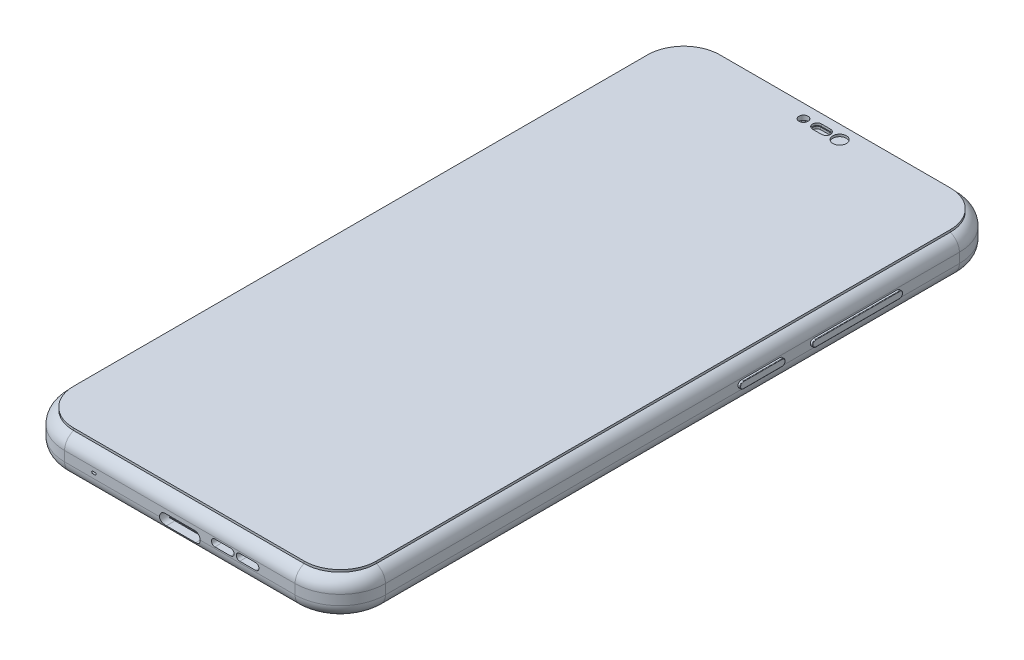
SolidWorks part; units mm, degrees
other "Camera1"
material "PMMA"
ref_plane "Front Plane" through (0, 0, 0) normal (0, 0, 1) x (1, 0, 0)
ref_plane "Top Plane" through (0, 0, 0) normal (0, 1, 0) x (1, 0, 0)
ref_plane "Right Plane" through (0, 0, 0) normal (1, 0, 0) x (0, 0, -1)
sketch "Sketch1" plane through (0, 0, 0) normal (0, 1, 0) x (1, 0, 0)
  line L1 (-25.5, 73.5) -> (25.5, 73.5)
  line L2 (-35.5, 63.5) -> (-35.5, -63.5)
  line L3 (-25.5, -73.5) -> (25.5, -73.5)
  line L4 (35.5, 63.5) -> (35.5, -63.5)
  line L5 (-35.5, 73.5) -> (35.5, -73.5) construction
  line L6 (-35.5, -73.5) -> (35.5, 73.5) construction
  arc A0 (-35.5, -63.5) -> (-25.5, -73.5) centre (-25.5, -63.5) ccw
  arc A1 (25.5, -73.5) -> (35.5, -63.5) centre (25.5, -63.5) ccw
  arc A2 (25.5, 73.5) -> (35.5, 63.5) centre (25.5, 63.5) cw
  arc A3 (-25.5, 73.5) -> (-35.5, 63.5) centre (-25.5, 63.5) ccw
  point P0 (0, 0)
  dimension "D3" = 10
  dimension "D1" = 147
  dimension "D2" = 71
extrude "Boss-Extrude1" add sketch "Sketch1" along normal blind 8
sketch "Sketch2" plane through (0, 8, 0) normal (0, 1, 0) x (1, 0, 0)
  line L24 (-25.5, -71.5) -> (25.5, -71.5)
  line L25 (33.5, -63.5) -> (33.5, 63.5)
  line L26 (-33.5, 63.5) -> (-33.5, -63.5)
  line L27 (25.5, 71.5) -> (-25.5, 71.5)
  line L28 (-25.5, -71.5) -> (25.5, -71.5)
  line L29 (33.5, -63.5) -> (33.5, 63.5)
  line L30 (-33.5, 63.5) -> (-33.5, -63.5)
  line L31 (25.5, 71.5) -> (-25.5, 71.5)
  arc A20 (-33.5, -63.5) -> (-25.5, -71.5) centre (-25.5, -63.5) ccw
  arc A21 (25.5, -71.5) -> (33.5, -63.5) centre (25.5, -63.5) ccw
  arc A22 (33.5, 63.5) -> (25.5, 71.5) centre (25.5, 63.5) ccw
  arc A23 (-25.5, 71.5) -> (-33.5, 63.5) centre (-25.5, 63.5) ccw
  arc A24 (-33.5, -63.5) -> (-25.5, -71.5) centre (-25.5, -63.5) ccw
  arc A25 (25.5, -71.5) -> (33.5, -63.5) centre (25.5, -63.5) ccw
  arc A26 (33.5, 63.5) -> (25.5, 71.5) centre (25.5, 63.5) ccw
  arc A27 (-25.5, 71.5) -> (-33.5, 63.5) centre (-25.5, 63.5) ccw
  dimension "D1" = 2
extrude "Boss-Extrude2" add sketch "Sketch2" along normal blind 0.5
fillet "Fillet1" radius 3 16 edges at (-32.5711, 0, 70.5711) (-35.5, 0, 0) (-32.5711, 0, -70.5711) (0, 0, -73.5) (32.5711, 0, -70.5711) (35.5, 0, 0) (32.5711, 0, 70.5711) (-32.5711, 8, 70.5711) (-35.5, 8, 0) (-32.5711, 8, -70.5711) (0, 8, -73.5) (32.5711, 8, -70.5711) (35.5, 8, 0) (32.5711, 8, 70.5711) (0, 0, 73.5) (0, 8, 73.5)
sketch "Sketch3" plane through (0, 0, 0) normal (0, -1, 0) x (1, 0, 0)
  line L0 (0, 0) -> (0, -50000) construction
  line L1 (0, -58.5) -> (0, -40.5) construction
  line L2 (-6, -58.5) -> (-6, -40.5)
  line L3 (6, -58.5) -> (6, -40.5)
  line L4 (25.5, -73.5) -> (-25.5, -73.5) construction
  arc A0 (-6, -58.5) -> (6, -58.5) centre (0, -58.5) ccw
  arc A1 (6, -40.5) -> (-6, -40.5) centre (0, -40.5) ccw
  point P5 (0, -49.5)
  point P10 (0, -64.5)
  point P11 (0, -34.5)
  dimension "D1" = 30
  dimension "D2" = 12
  dimension "D3" = 9
extrude "Boss-Extrude3" add sketch "Sketch3" along normal blind 1
fillet "Fillet2" radius 1 4 edges at (-6, -1, -49.5) (0, -1, -34.5) (6, -1, -49.5) (0, -1, -64.5)
sketch "Sketch4" plane through (0, -1, 0) normal (0, -1, 0) x (1, 0, 0)
  line L0 (-5, -40.5) -> (-5, -58.5) construction
  line L1 (5, -58.5) -> (5, -40.5) construction
  line L2 (-5, -40.5) -> (-5, -58.5)
  line L3 (5, -58.5) -> (5, -40.5)
  arc A0 (5, -40.5) -> (-5, -40.5) centre (0, -40.5) ccw construction
  arc A1 (-5, -58.5) -> (5, -58.5) centre (0, -58.5) ccw construction
  arc A2 (5, -40.5) -> (-5, -40.5) centre (0, -40.5) ccw
  arc A3 (-5, -58.5) -> (5, -58.5) centre (0, -58.5) ccw
extrude "Cut-Extrude1" cut sketch "Sketch4" against normal blind 1
sketch "Sketch5" plane through (0, 0, 0) normal (0, -1, 0) x (1, 0, 0)
  line L2 (-5, -40.5) -> (-5, -58.5)
  line L3 (5, -58.5) -> (5, -40.5)
  line L4 (-5, -40.5) -> (-5, -58.5)
  line L5 (5, -58.5) -> (5, -40.5)
  circle A0 centre (0, -58.5) radius 2
  circle A1 centre (0, -49.5) radius 2
  arc A2 (5, -40.5) -> (-5, -40.5) centre (0, -40.5) ccw
  arc A3 (-5, -58.5) -> (5, -58.5) centre (0, -58.5) ccw
  arc A4 (5, -40.5) -> (-5, -40.5) centre (0, -40.5) ccw
  arc A5 (-5, -58.5) -> (5, -58.5) centre (0, -58.5) ccw
  point P11 (-5, -49.5)
  dimension "D2" = 4
  dimension "D3" = 4
  dimension "D1" = 0
extrude "Cut-Extrude2" cut sketch "Sketch5" against normal blind 0.5 contours A0 | A1 region at (0, 0, -58.5) region at (0, 0, -49.5)
sketch "Sketch6" plane through (0, 0.5, 0) normal (0, -1, 0) x (1, 0, 0)
  circle A0 centre (0, -49.5) radius 1
  circle A1 centre (0, -49.5) radius 2
  circle A2 centre (0, -49.5) radius 2
  circle A3 centre (0, -58.5) radius 2
  circle A4 centre (0, -58.5) radius 2
  circle A5 centre (0, -58.5) radius 0.5
  dimension "D3" = 2
  dimension "D4" = 1
  dimension "D1" = 0
  dimension "D2" = 0
extrude "Boss-Extrude4" add sketch "Sketch6" along normal blind 0.5 contours A5 | A0 region at (0, 0.5, -49.5) region at (0, 0.5, -58.5)
fillet "Fillet3" radius 0.5 2 edges at (0, 0, -50.5) (0, 0, -59)
sketch "Sketch7" plane through (0, 0, 0) normal (0, -1, 0) x (1, 0, 0)
  line L2 (-5, -40.5) -> (-5, -58.5)
  line L3 (5, -58.5) -> (5, -40.5)
  line L4 (-5, -40.5) -> (-5, -58.5)
  line L5 (5, -58.5) -> (5, -40.5)
  circle A0 centre (0, -40.5) radius 2.5
  arc A2 (5, -40.5) -> (-5, -40.5) centre (0, -40.5) ccw
  arc A3 (-5, -58.5) -> (5, -58.5) centre (0, -58.5) ccw
  arc A4 (5, -40.5) -> (-5, -40.5) centre (0, -40.5) ccw
  arc A5 (-5, -58.5) -> (5, -58.5) centre (0, -58.5) ccw
  dimension "D2" = 5
  dimension "D1" = 0
extrude "Boss-Extrude5" add sketch "Sketch7" along normal blind 0.5 contours A0 region at (0, 0, -40.5)
ref_plane "Plane1" through (0, -1, 0) normal (0, -1, 0) x (-1, 0, 0)
sketch "Sketch8" plane through (0, -1, 0) normal (0, -1, 0) x (-1, 0, 0)
  line L0 (5, 40.5) -> (5, 58.5) construction
  line L1 (-5, 58.5) -> (-5, 40.5) construction
  line L2 (5, 40.5) -> (5, 58.5)
  line L3 (-5, 58.5) -> (-5, 40.5)
  line L4 (4.8, 40.5) -> (4.8, 58.5)
  line L5 (-4.8, 58.5) -> (-4.8, 40.5)
  arc A0 (-5, 40.5) -> (5, 40.5) centre (0, 40.5) ccw construction
  arc A1 (5, 58.5) -> (-5, 58.5) centre (0, 58.5) ccw construction
  arc A2 (-5, 40.5) -> (5, 40.5) centre (0, 40.5) ccw
  arc A3 (5, 58.5) -> (-5, 58.5) centre (0, 58.5) ccw
  arc A4 (-4.8, 40.5) -> (4.8, 40.5) centre (0, 40.5) ccw
  arc A5 (4.8, 58.5) -> (-4.8, 58.5) centre (0, 58.5) ccw
  dimension "D1" = 0.2
extrude "Boss-Extrude6" add sketch "Sketch8" against normal up to surface (1 mm away) up to face at (0, 0, -43)
sketch "Sketch9" plane through (0, -1, 0) normal (0, -1, 0) x (-1, 0, 0)
  line L0 (4.8, 40.5) -> (4.8, 58.5) construction
  line L1 (-4.8, 58.5) -> (-4.8, 40.5) construction
  line L2 (4.8, 40.5) -> (4.8, 58.5)
  line L3 (-4.8, 58.5) -> (-4.8, 40.5)
  line L4 (-4.7, 58.5) -> (-4.7, 40.5)
  line L5 (4.7, 40.5) -> (4.7, 58.5)
  arc A0 (-4.8, 40.5) -> (4.8, 40.5) centre (0, 40.5) ccw construction
  arc A1 (4.8, 58.5) -> (-4.8, 58.5) centre (0, 58.5) ccw construction
  arc A2 (-4.8, 40.5) -> (4.8, 40.5) centre (0, 40.5) ccw
  arc A3 (4.8, 58.5) -> (-4.8, 58.5) centre (0, 58.5) ccw
  arc A4 (4.7, 58.5) -> (-4.7, 58.5) centre (0, 58.5) ccw
  arc A5 (-4.7, 40.5) -> (4.7, 40.5) centre (0, 40.5) ccw
  dimension "D1" = 0.1
extrude "Boss-Extrude7" add sketch "Sketch9" against normal blind 0.2 contours L4 A5 L5 A4 region at (0, -1, -49.5)
sketch "Sketch10" plane through (0, 0, 0) normal (0, -1, 0) x (1, 0, 0)
  circle A0 centre (0, -25.5) radius 5
  arc A1 (6, -40.5) -> (-6, -40.5) centre (0, -40.5) ccw construction
  point P5 (0, -34.5)
  dimension "D1" = 10
  dimension "D2" = 9
extrude "Cut-Extrude3" cut sketch "Sketch10" against normal blind 0.2
chamfer "Chamfer1" distance 0.2 angle 45 1 edges at (0, 0.2, -30.5)
sketch "Sketch13" plane through (0, 0, -73.5) normal (0, 0, -1) x (-1, 0, 0)
  line L0 (-25.5, 3) -> (25.5, 3) construction
  line L1 (-35.5, 5.1716) -> (-35.5, 3) construction
  circle A0 centre (-21.5, 3) radius 2
  dimension "D1" = 4
  dimension "D2" = 14
extrude "Cut-Extrude4" cut sketch "Sketch13" against normal blind 10
sketch "Sketch14" plane through (-35.5, 0, 0) normal (-1, 0, 0) x (0, 0, 1)
  line L0 (-41.5, 4.0858) -> (-25.5, 4.0858) construction
  line L1 (-41.5, 5.0858) -> (-25.5, 5.0858)
  line L2 (-41.5, 3.0858) -> (-25.5, 3.0858)
  line L3 (-63.5, 5.1716) -> (-63.5, 3) construction
  line L4 (-73.5, 5.1716) -> (-73.5, 3) construction
  line L5 (-41.5, 4.9858) -> (-25.5, 4.9858)
  line L6 (-41.5, 3.1858) -> (-25.5, 3.1858)
  arc A0 (-41.5, 5.0858) -> (-41.5, 3.0858) centre (-41.5, 4.0858) ccw
  arc A1 (-25.5, 3.0858) -> (-25.5, 5.0858) centre (-25.5, 4.0858) ccw
  arc A2 (-25.5, 3.1858) -> (-25.5, 4.9858) centre (-25.5, 4.0858) ccw
  arc A3 (-41.5, 4.9858) -> (-41.5, 3.1858) centre (-41.5, 4.0858) ccw
  circle A4 centre (-25.5, 4.0858) radius 0.25
  point P2 (-33.5, 4.0858)
  point P10 (-63.5, 4.0858)
  point P11 (-42.5, 4.0858)
  point P12 (-24.5, 4.0858)
  dimension "D5" = 0.5
  dimension "D1" = 18
  dimension "D2" = 2
  dimension "D3" = 31
  dimension "D4" = 0.1
extrude "Cut-Extrude5" cut sketch "Sketch14" against normal blind 1 contours A4 | L2 A1 L1 A0 A3 L5 A2 L6 region at (-35.5, 5.0677, -33.5) region at (-35.5, 4.0858, -25.5)
sketch "Sketch15" plane through (0, 0, 73.5) normal (0, 0, 1) x (1, 0, 0)
  line L0 (-25.5, 4.0858) -> (25.5, 4.0858) construction
  line L1 (-25.5, 5.1716) -> (-25.5, 3) construction
  line L2 (25.5, 5.1716) -> (25.5, 3) construction
  line L3 (7.75, 4.0858) -> (11.25, 4.0858) construction
  line L4 (7.75, 4.8358) -> (11.25, 4.8358)
  line L5 (7.75, 3.3358) -> (11.25, 3.3358)
  line L6 (13.25, 4.0858) -> (16.75, 4.0858) construction
  line L7 (13.25, 4.8358) -> (16.75, 4.8358)
  line L8 (13.25, 3.3358) -> (16.75, 3.3358)
  line L9 (35.5, 5.1716) -> (35.5, 3) construction
  line L10 (-19.25, 4.0858) -> (-18.75, 4.0858) construction
  line L11 (-19.25, 4.3358) -> (-18.75, 4.3358)
  line L12 (-19.25, 3.8358) -> (-18.75, 3.8358)
  line L13 (-35.5, 5.1716) -> (-35.5, 3) construction
  arc A0 (7.75, 4.8358) -> (7.75, 3.3358) centre (7.75, 4.0858) ccw
  arc A1 (11.25, 3.3358) -> (11.25, 4.8358) centre (11.25, 4.0858) ccw
  arc A2 (13.25, 4.8358) -> (13.25, 3.3358) centre (13.25, 4.0858) ccw
  arc A3 (16.75, 3.3358) -> (16.75, 4.8358) centre (16.75, 4.0858) ccw
  arc A4 (-19.25, 4.3358) -> (-19.25, 3.8358) centre (-19.25, 4.0858) ccw
  arc A5 (-18.75, 3.8358) -> (-18.75, 4.3358) centre (-18.75, 4.0858) ccw
  point P8 (9.5, 4.0858)
  point P13 (15, 4.0858)
  point P20 (12.5, 4.0858)
  point P21 (17.5, 4.0858)
  point P22 (-19, 4.0858)
  point P27 (12, 4.0858)
  point P32 (-19.5, 4.0858)
  point P33 (-18.5, 4.0858)
  dimension "D1" = 5
  dimension "D2" = 1.5
  dimension "D3" = 18
  dimension "D4" = 0.5
  dimension "D5" = 0.5
  dimension "D6" = 1
  dimension "D7" = 16
extrude "Cut-Extrude6" cut sketch "Sketch15" against normal blind 2
sketch "Sketch17" plane through (0, 0, 73.5) normal (0, 0, 1) x (1, 0, 0)
  line L0 (-3.25, 3) -> (3.25, 3) construction
  line L1 (-25.5, 3) -> (25.5, 3) construction
  line L2 (-3.25, 4.25) -> (3.25, 4.25)
  line L3 (-3.25, 1.75) -> (3.25, 1.75)
  line L5 (-3.25, 2.9) -> (3.25, 2.9)
  line L6 (-3.25, 2.9) -> (-3.25, 3.1)
  line L7 (-3.25, 3.1) -> (3.25, 3.1)
  line L8 (3.25, 2.9) -> (3.25, 3.1)
  line L9 (-3.25, 2.9) -> (3.25, 3.1) construction
  line L10 (-3.25, 3.1) -> (3.25, 2.9) construction
  arc A0 (-3.25, 4.25) -> (-3.25, 1.75) centre (-3.25, 3) ccw
  arc A1 (3.25, 1.75) -> (3.25, 4.25) centre (3.25, 3) ccw
  point P4 (0, 3)
  point P10 (-4.5, 3)
  point P12 (4.5, 3)
  point P13 (0, 3)
  dimension "D1" = 2.5
  dimension "D2" = 9
  dimension "D3" = 0.2
extrude "Cut-Extrude7" cut sketch "Sketch17" against normal blind 4
sketch "Sketch18" plane through (0, 0, 73.5) normal (0, 0, 1) x (1, 0, 0)
  line L4 (3.25, 3) -> (3.25, 3.1)
  line L5 (3.25, 3.1) -> (-3.25, 3.1)
  line L6 (-3.25, 3.1) -> (-3.25, 3)
  line L7 (-3.25, 3) -> (3.25, 3)
  line L8 (3.25, 3) -> (3.25, 3.1)
  line L9 (3.25, 3.1) -> (-3.25, 3.1)
  line L10 (-3.25, 3.1) -> (-3.25, 3)
  line L11 (-3.25, 3) -> (3.25, 3)
  line L12 (-3.25, 2.9) -> (3.25, 2.9)
  line L13 (3.25, 2.9) -> (3.25, 3)
  line L14 (3.25, 3) -> (-3.25, 3)
  line L15 (-3.25, 3) -> (-3.25, 2.9)
  line L16 (-3.25, 2.9) -> (3.25, 2.9)
  line L17 (3.25, 2.9) -> (3.25, 3)
  line L18 (3.25, 3) -> (-3.25, 3)
  line L19 (-3.25, 3) -> (-3.25, 2.9)
  line M9 (3.25, 3) -> (3.25, 3.1)
  line M10 (3.25, 3.1) -> (-3.25, 3.1)
  line M11 (-3.25, 3.1) -> (-3.25, 3)
  line M12 (-3.25, 3) -> (3.25, 3)
  dimension "D1" = 0
  dimension "D2" = 0
extrude "Cut-Extrude8" cut sketch "Sketch18" against normal blind 1 contours M12 M9 M10 M11 | L19 L16 L17 M12 region at (0, 3.05, 73.5) region at (0, 2.95, 73.5)
sketch "Sketch19" plane through (35.5, 0, 0) normal (1, 0, 0) x (0, 0, -1)
  line L0 (-63.5, 4.0858) -> (63.5, 4.0858) construction
  line L1 (-63.5, 5.1716) -> (-63.5, 3) construction
  line L2 (63.5, 5.1716) -> (63.5, 3) construction
  line L3 (31.25, 4.0858) -> (49.75, 4.0858) construction
  line L4 (31.25, 4.8358) -> (49.75, 4.8358)
  line L5 (31.25, 3.3358) -> (49.75, 3.3358)
  line L6 (15.25, 4.0858) -> (23.75, 4.0858) construction
  line L7 (15.25, 4.8358) -> (23.75, 4.8358)
  line L8 (15.25, 3.3358) -> (23.75, 3.3358)
  line L10 (73.5, 5.1716) -> (73.5, 3) construction
  arc A0 (31.25, 4.8358) -> (31.25, 3.3358) centre (31.25, 4.0858) ccw
  arc A1 (49.75, 3.3358) -> (49.75, 4.8358) centre (49.75, 4.0858) ccw
  arc A2 (15.25, 4.8358) -> (15.25, 3.3358) centre (15.25, 4.0858) ccw
  arc A3 (23.75, 3.3358) -> (23.75, 4.8358) centre (23.75, 4.0858) ccw
  point P8 (40.5, 4.0858)
  point P13 (19.5, 4.0858)
  point P21 (30.5, 4.0858)
  point P22 (50.5, 4.0858)
  point P23 (24.5, 4.0858)
  point P24 (14.5, 4.0858)
  dimension "D1" = 1.5
  dimension "D2" = 20
  dimension "D3" = 6
  dimension "D4" = 10
  dimension "D5" = 23
extrude "Boss-Extrude8" add sketch "Sketch19" along normal blind 0.5
fillet "Fillet4" radius 0.1 8 edges at (36, 3.3358, -40.5) (36, 4.0858, -30.5) (36, 4.8358, -40.5) (36, 4.0858, -24.5) (36, 3.3358, -19.5) (36, 4.0858, -14.5) (36, 4.0858, -50.5) (36, 4.8358, -19.5)
ref_plane "Plane3" through (33.5, 8, 63.5) normal (0, -1, 0) x (-1, 0, 0)
sketch "Sketch20" plane through (33.5, 8, 63.5) normal (0, -1, 0) x (1, 0, 0)
  line L0 (-38.3096, -132) -> (49961.6904, -132) construction
  line L1 (-34.5, -132) -> (-32.5, -132) construction
  line L2 (-34.5, -131) -> (-32.5, -131)
  line L3 (-34.5, -133) -> (-32.5, -133)
  line L4 (-8, 8) -> (-59, 8)
  line L5 (0, -127) -> (0, 0)
  line L6 (-59, -135) -> (-8, -135)
  line L7 (-67, 0) -> (-67, -127)
  line L8 (-8, 8) -> (-59, 8)
  line L9 (0, -127) -> (0, 0)
  line L10 (-59, -135) -> (-8, -135)
  line L11 (-67, 0) -> (-67, -127)
  arc A0 (-34.5, -131) -> (-34.5, -133) centre (-34.5, -132) ccw
  arc A1 (-32.5, -133) -> (-32.5, -131) centre (-32.5, -132) ccw
  circle A2 centre (-29.5, -132) radius 1.5
  arc A4 (-59, 8) -> (-67, 0) centre (-59, 0) ccw
  arc A5 (0, 0) -> (-8, 8) centre (-8, 0) ccw
  arc A6 (-8, -135) -> (0, -127) centre (-8, -127) ccw
  arc A7 (-67, -127) -> (-59, -135) centre (-59, -127) ccw
  arc A8 (-59, 8) -> (-67, 0) centre (-59, 0) ccw
  arc A9 (0, 0) -> (-8, 8) centre (-8, 0) ccw
  arc A10 (-8, -135) -> (0, -127) centre (-8, -127) ccw
  arc A11 (-67, -127) -> (-59, -135) centre (-59, -127) ccw
  point P16 (-33.5, -132)
  point P22 (-33.5, -135)
  point P23 (-31.5, -132)
  point P24 (-35.5, -132)
  dimension "D5" = 3
  dimension "D2" = 3
  dimension "D3" = 2
  dimension "D4" = 4
  dimension "D6" = 2
  dimension "D1" = 0
extrude "Cut-Extrude9" cut sketch "Sketch20" against normal blind 0.5 contours L3 A1 L2 A0 | A2 region at (0, 8, -68.5) region at (4, 8, -68.5)
sketch "Sketch21" plane through (0, 8, 0) normal (0, 1, 0) x (1, 0, 0)
  line L0 (1, 69.3) -> (-1, 69.3)
  line L1 (-1, 67.7) -> (1, 67.7)
  line L2 (1, 69.5) -> (-1, 69.5)
  line L3 (-1, 67.5) -> (1, 67.5)
  line L4 (1, 69.5) -> (-1, 69.5)
  line L5 (-1, 67.5) -> (1, 67.5)
  arc A0 (-1, 69.3) -> (-1, 67.7) centre (-1, 68.5) ccw
  arc A1 (1, 67.7) -> (1, 69.3) centre (1, 68.5) ccw
  arc A2 (-1, 69.5) -> (-1, 67.5) centre (-1, 68.5) ccw
  arc A3 (1, 67.5) -> (1, 69.5) centre (1, 68.5) ccw
  arc A4 (-1, 69.5) -> (-1, 67.5) centre (-1, 68.5) ccw
  arc A5 (1, 67.5) -> (1, 69.5) centre (1, 68.5) ccw
  circle A6 centre (-4, 68.5) radius 1
  point P14 (-2, 68.5)
  dimension "D4" = 2
  dimension "D3" = 2
  dimension "D1" = 0
  dimension "D2" = 0.2
extrude "Cut-Extrude10" cut sketch "Sketch21" against normal blind 0.5 and the other way blind 0.5 contours L1 A1 L0 A0 | A6 region at (0, 8, -68.5) region at (-4, 8, -68.5)
sketch "Sketch22" plane through (0, 7.5, 0) normal (0, 1, 0) x (1, 0, 0)
  circle A0 centre (-4, 68.5) radius 0.5
  circle A1 centre (-4, 68.5) radius 1
  circle A2 centre (-4, 68.5) radius 1
  dimension "D2" = 1
  dimension "D1" = 0
extrude "Boss-Extrude9" add sketch "Sketch22" along normal blind 0.5 contours A0 region at (-4, 7.5, -68.5)
fillet "Fillet5" radius 0.5 1 edges at (-4, 8, -68)
sketch "Sketch23" [suppressed] plane through (0, 8.5, 0) normal (0, 1, 0) x (1, 0, 0)
  text T0 "                  NOKIA" font "Franklin Gothic Medium" height in points 8
extrude "Boss-Extrude10" [suppressed] add sketch "Sketch23" along normal blind 0.1
sketch "Sketch24" [suppressed] plane through (0, 0, 0) normal (0, -1, 0) x (1, 0, 0)
  line L0 (0, 70.5) -> (0, -70.5) construction
  line L1 (25.5, 70.5) -> (-25.5, 70.5) construction
  line L2 (25.5, 70.5) -> (-25.5, 70.5) construction
  line L3 (-25.5, -70.5) -> (25.5, -70.5) construction
  line L4 (-25.5, -70.5) -> (25.5, -70.5) construction
  line L5 (-1, 70.5) -> (-1, -70.5) construction
  text T0 "NOKIA" font "Franklin Gothic Medium" height in points 8
  dimension "D1" = 1
extrude "Boss-Extrude11" [suppressed] add sketch "Sketch24" along normal blind 0.1
